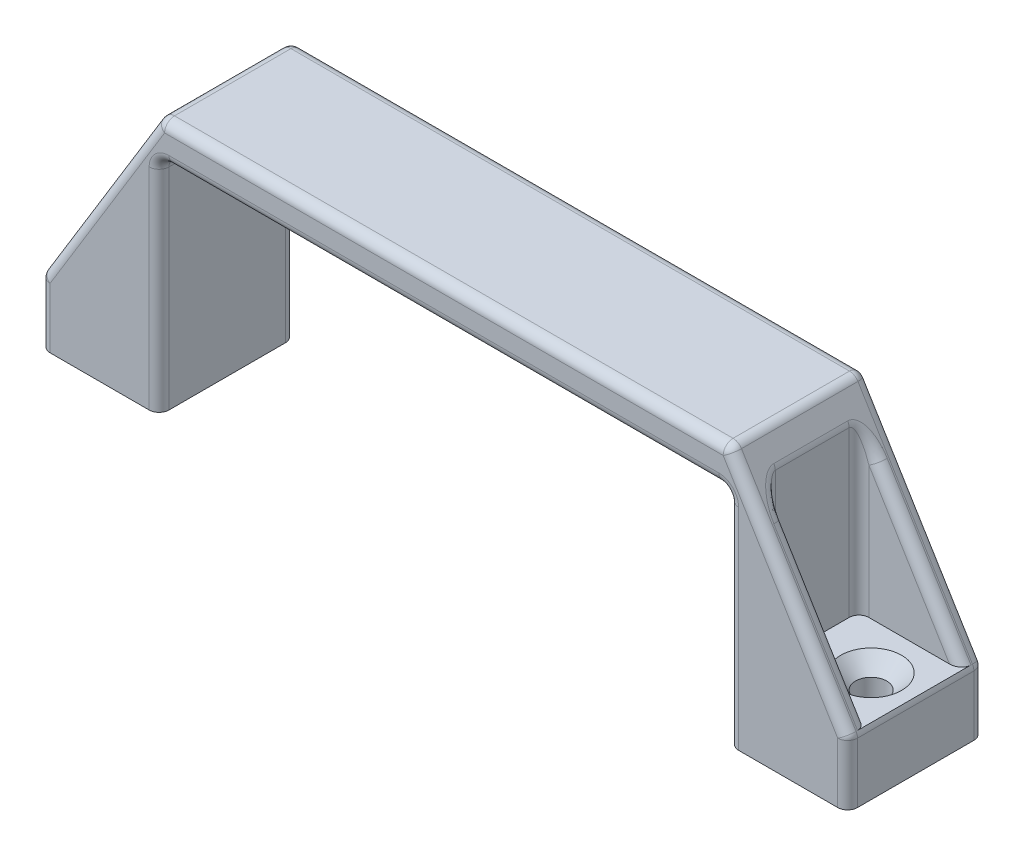
SolidWorks part; units mm, degrees
material "ABS"
ref_plane "Přední rovina" through (0, 0, 0) normal (0, 0, 1) x (1, 0, 0)
ref_plane "Horní rovina" through (0, 0, 0) normal (0, 1, 0) x (1, 0, 0)
ref_plane "Pravá rovina" through (0, 0, 0) normal (1, 0, 0) x (0, 0, -1)
sketch "Skica1" plane through (0, 0, 0) normal (0, 0, 1) x (1, 0, 0)
  line L0 (-60.9746, 0) -> (-36.9746, 0)
  line L1 (-60.9746, 0) -> (-60.9746, 12.1376)
  line L2 (-60.6815, 13.18) -> (-37.5594, 51.0424)
  line L3 (-35.8525, 52) -> (76.9034, 52)
  line L4 (78.6102, 51.0424) -> (101.7323, 13.18)
  line L5 (102.0254, 12.1376) -> (102.0254, 0)
  line L6 (-36.9746, 42.5) -> (-36.9746, 0)
  line L7 (-34.9746, 44.5) -> (76.0254, 44.5)
  line L8 (78.0254, 42.5) -> (78.0254, 0)
  line L9 (78.0254, 0) -> (102.0254, 0)
  arc A0 (-34.9746, 44.5) -> (-36.9746, 42.5) centre (-34.9746, 42.5) ccw
  arc A1 (-35.8525, 52) -> (-37.5594, 51.0424) centre (-35.8525, 50) ccw
  arc A2 (78.6102, 51.0424) -> (76.9034, 52) centre (76.9034, 50) ccw
  arc A3 (78.0254, 42.5) -> (76.0254, 44.5) centre (76.0254, 42.5) ccw
  arc A4 (102.0254, 12.1376) -> (101.7323, 13.18) centre (100.0254, 12.1376) ccw
  arc A5 (-60.9746, 12.1376) -> (-60.6815, 13.18) centre (-58.9746, 12.1376) cw
  point P13 (-36.9746, 44.5)
  point P16 (-36.9746, 52)
  point P19 (78.0254, 52)
  point P22 (78.0254, 44.5)
  point P25 (102.0254, 12.7)
  point P28 (-60.9746, 12.7)
  dimension "D8" = 2
  dimension "D1" = 163
  dimension "D2" = 24
  dimension "D3" = 24
  dimension "D4" = 44.5
  dimension "D5" = 52
  dimension "D6" = 12.7
  dimension "D7" = 12.7
extrude "Vysunout1" add sketch "Skica1" along normal blind 27.5
sketch "Skica3" plane through (102.0254, 0, 0) normal (1, 0, 0) x (0, 0, -1)
  line L0 (-27.5, 13.18) -> (0, 13.18) construction
  line L1 (-23.2, 13.18) -> (-4.3, 13.18)
  line L2 (-23.2, 13.18) -> (-23.2, 51.0424)
  line L3 (-23.2, 51.0424) -> (-4.3, 51.0424)
  line L4 (-4.3, 13.18) -> (-4.3, 51.0424)
  line L5 (-27.5, 51.0424) -> (0, 51.0424) construction
  line L6 (0, 13.18) -> (0, 51.0424) construction
  line L7 (-27.5, 13.18) -> (-27.5, 51.0424) construction
  dimension "D1" = 4.3
  dimension "D2" = 4.3
extrude "Odebrat vysunutím1" cut sketch "Skica3" against normal blind 20.9
sketch "Skica4" plane through (-60.9746, 0, 0) normal (-1, 0, 0) x (0, 0, 1)
  line L0 (27.5, 13.18) -> (0, 13.18) construction
  line L1 (4.3, 13.18) -> (23.2, 13.18)
  line L2 (4.3, 13.18) -> (4.3, 51.0424)
  line L3 (4.3, 51.0424) -> (23.2, 51.0424)
  line L4 (23.2, 13.18) -> (23.2, 51.0424)
  line L5 (27.5, 51.0424) -> (0, 51.0424) construction
  line L6 (0, 51.0424) -> (0, 13.18) construction
  line L7 (27.5, 51.0424) -> (27.5, 13.18) construction
  dimension "D1" = 4.3
  dimension "D2" = 4.3
extrude "Odebrat vysunutím2" cut sketch "Skica4" against normal blind 20.9
sketch "Skica5" plane through (0, 13.18, 0) normal (0, 1, 0) x (-1, 0, 0)
  line L0 (-101.7323, 13.75) -> (60.6815, 13.75) construction
  line L1 (-101.7323, 23.2) -> (-101.7323, 4.3) construction
  line L2 (60.6815, 23.2) -> (60.6815, 4.3) construction
  line L3 (51.9746, 6.3) -> (51.9746, 21.2) construction
  line L4 (-93.0254, 6.3) -> (-93.0254, 21.2) construction
  line L5 (-81.1254, 4.3) -> (-101.7323, 4.3) construction
  line L6 (-81.1254, 23.2) -> (-101.7323, 23.2) construction
  line L7 (40.0746, 4.3) -> (60.6815, 4.3) construction
  line L8 (40.0746, 23.2) -> (60.6815, 23.2) construction
  line L9 (60.9746, 27.5) -> (60.9746, 0) construction
  line L10 (-102.0254, 27.5) -> (-102.0254, 0) construction
  circle A0 centre (-93.0254, 13.75) radius 3.15
  circle A1 centre (51.9746, 13.75) radius 3.15
  dimension "D8" = 6.3
  dimension "D9" = 6.3
  dimension "D1" = 2
  dimension "D2" = 2
  dimension "D3" = 2
  dimension "D4" = 2
  dimension "D5" = 145
  dimension "D6" = 9
  dimension "D7" = 9
extrude "Odebrat vysunutím3" cut sketch "Skica5" against normal through all
chamfer "Zkosit1" distance 3 angle 45 2 edges at (-51.9746, 13.18, 16.9) (93.0254, 13.18, 16.9)
fillet "Zaoblit1" radius 2 28 edges at (-36.9746, 21.25, 0) (-36.3888, 43.9142, 0) (78.0254, 21.25, 0) (77.4396, 43.9142, 0) (78.0254, 21.25, 27.5) (77.4396, 43.9142, 27.5) (20.5254, 44.5, 27.5) (-36.3888, 43.9142, 27.5) (102.0254, 6.0688, 27.5) (101.9508, 12.679, 27.5) (90.1713, 32.1112, 27.5) (77.8819, 51.7442, 27.5) (-60.9746, 6.0688, 27.5) (-60.8999, 12.679, 27.5) (-49.1204, 32.1112, 27.5) (-36.8311, 51.7442, 27.5) (102.0254, 6.0688, 0) (101.9508, 12.679, 0) (90.1713, 32.1112, 0) (77.8819, 51.7442, 0) (-60.9746, 6.0688, 0) (-60.8999, 12.679, 0) (-49.1204, 32.1112, 0) (-36.8311, 51.7442, 0) (20.5254, 44.5, 0) (-36.9746, 21.25, 27.5) (20.5254, 52, 27.5) (20.5254, 52, 0)
fillet "Zaoblit2" radius 2 10 edges at (81.1254, 46.9238, 13.75) (91.4289, 30.0519, 23.2) (91.4289, 30.0519, 4.3) (81.1254, 30.0519, 4.3) (81.1254, 30.0519, 23.2) (-40.0746, 30.0519, 4.3) (-40.0746, 30.0519, 23.2) (-50.378, 30.0519, 23.2) (-40.0746, 46.9238, 13.75) (-50.378, 30.0519, 4.3)
scale "Scale1" bodies to scale 104 scale about centroid uniform scaling yes scale factor 0.5
